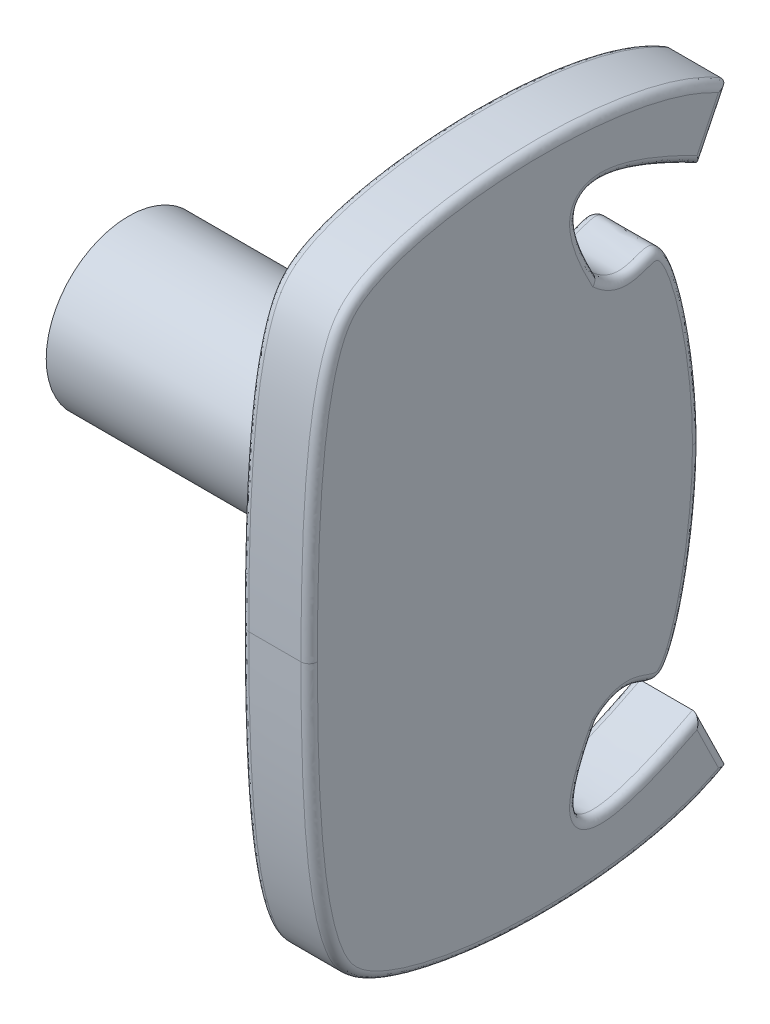
SolidWorks part; units mm, degrees
ref_plane "Piano frontale" through (0, 0, 0) normal (1, 0, 0) x (0, 1, 0)
ref_plane "Piano superiore" through (0, 0, 0) normal (0, 0, 1) x (0, 1, 0)
ref_plane "Piano destro" through (0, 0, 0) normal (0, 1, 0) x (-1, 0, 0)
sketch "Schizzo2" plane through (0, 0, 0) normal (1, 0, 0) x (0, 1, 0)
  line L0 (30.8977, 282.6657) -> (776.8977, 282.6657) construction
  line L1 (0, -55) -> (0, 55) construction
  line L2 (0, 134.8705) -> (75.2737, 134.8705) construction
  line L3 (-107.7042, -18.1484) -> (-86.5453, -7.7834)
  line L4 (0, -7.7834) -> (46.076, -7.7834) construction
  line L5 (0, 134.8705) -> (0, -7.7834)
  spline S0 degree 3 poles (-107.7042, -18.1484) (-128.5924, 15.8168) (-123.9116, 108.9165) (-89.0273, 131.3297) (-49.7695, 134.8705) (0, 134.8705) knots 0 0 0 0 0.555712 0.655712 1 1 1 1
  spline S1 degree 2 poles (-86.5453, -7.7834) (-119.4851, 55.6565) (-70.0757, 29.2167) knots 0 0 0 1 1 1
  spline S2 degree 3 poles (-70.0757, 29.2167) (-58.7612, 16.4059) (-87.8377, 4.6565) (-27.0712, -7.7834) (0, -7.7834) knots 0 0 0 0 0.484242 1 1 1 1
extrude "Estrusione-Estrusione2" add sketch "Schizzo2" along normal blind 25
mirror "Specchia1" about plane through (0, 0, 0) normal (0, 1, 0) of bodies 102
fillet "Raccordo3" radius 3 16 edges at (0, -97.1247, -12.9659) (25, -97.1247, -12.9659) (0, 97.1247, -12.9659) (25, 97.1247, -12.9659)
sketch "Schizzo3" plane through (0, 0, 0) normal (-1, 0, 0) x (0, -1, 0)
  line L0 (0, 55) -> (0, -55) construction
  circle A0 centre (0, 55.6522) radius 30
  dimension "D1" = 60
extrude "Estrusione-Estrusione3" add sketch "Schizzo3" along normal blind 120
fillet "Raccordo4" radius 10 1 edges at (0, 0, 25.6522)
